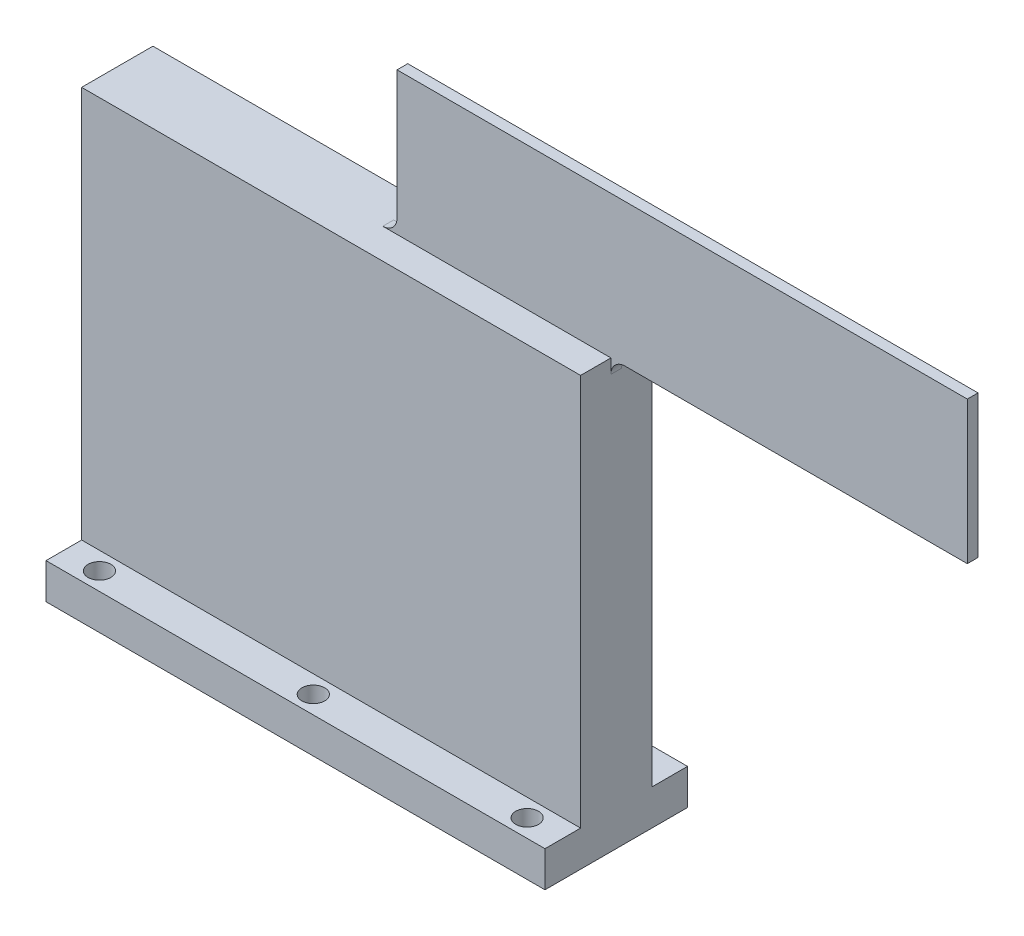
SolidWorks part; units mm, degrees
ref_plane "Plan de face" through (0, 0, 0) normal (0, 0, 1) x (1, 0, 0)
ref_plane "Plan de dessus" through (0, 0, 0) normal (0, 1, 0) x (1, 0, 0)
ref_plane "Plan de droite" through (0, 0, 0) normal (1, 0, 0) x (0, 0, -1)
sketch "Esquisse1" plane through (0, 0, 0) normal (0, 1, 0) x (1, 0, 0)
  line L1 (17.5, -2.5) -> (-17.5, -2.5)
  line L2 (17.5, -2.5) -> (17.5, 2.5)
  line L3 (17.5, 2.5) -> (-17.5, 2.5)
  line L4 (-17.5, -2.5) -> (-17.5, 2.5)
  line L5 (17.5, -2.5) -> (-17.5, 2.5) construction
  line L6 (17.5, 2.5) -> (-17.5, -2.5) construction
  point P0 (0, 0)
  dimension "D1" = 35
  dimension "D2" = 5
extrude "Boss.-Extru.1" add sketch "Esquisse1" along normal blind 30
sketch "Esquisse2" plane through (0, 30, 0) normal (0, 1, 0) x (1, 0, 0)
  line L1 (42.5, -0.375) -> (2.5, -0.375)
  line L2 (42.5, -0.375) -> (42.5, 0.375)
  line L3 (42.5, 0.375) -> (2.5, 0.375)
  line L4 (2.5, -0.375) -> (2.5, 0.375)
  line L5 (42.5, -0.375) -> (2.5, 0.375) construction
  line L6 (42.5, 0.375) -> (2.5, -0.375) construction
  line L8 (17.5, -2.5) -> (17.5, 2.5) construction
  point P0 (22.5, 0)
  point P7 (17.5, 0)
  dimension "D1" = 40
  dimension "D2" = 0.75
  dimension "D3" = 5
extrude "Boss.-Extru.2" add sketch "Esquisse2" along normal blind 10
fillet "Congé1" radius 1 2 edges at (2.5, 30, 0) (17.5, 30, 0)
sketch "Esquisse3" plane through (0, 0, 0) normal (0, -1, 0) x (1, 0, 0)
  line L0 (-17.5, -2.5) -> (-17.5, 2.5) construction
  line L1 (17.5, -5) -> (-17.5, -5)
  line L2 (17.5, -5) -> (17.5, 5)
  line L3 (17.5, 5) -> (-17.5, 5)
  line L4 (-17.5, -5) -> (-17.5, 5)
  line L5 (17.5, -5) -> (-17.5, 5) construction
  line L6 (17.5, 5) -> (-17.5, -5) construction
  point P0 (0, 0)
  dimension "D1" = 10
extrude "Boss.-Extru.3" add sketch "Esquisse3" against normal blind 2.5
sketch "Esquisse4" plane through (0, 2.5, 0) normal (0, 1, 0) x (1, 0, 0)
  line L0 (17.5, 5) -> (17.5, 2.5) construction
  line L1 (-22, 0) -> (22, 0) construction
  circle A0 centre (-15, 3.75) radius 0.8
  circle A1 centre (0, 3.75) radius 0.8
  circle A2 centre (15, 3.75) radius 0.8
  circle A3 centre (15, -3.75) radius 0.8
  circle A4 centre (0, -3.75) radius 0.8
  circle A5 centre (-15, -3.75) radius 0.8
  point P6 (0, 0)
  point P10 (17.5, 3.75)
  dimension "D1" = 1.6
  dimension "D2" = 15
  dimension "D3" = 15
extrude "Enlèv. mat.-Extru.1" cut sketch "Esquisse4" against normal up to surface (2.5 mm away) up to face at (0, 0, 0)
